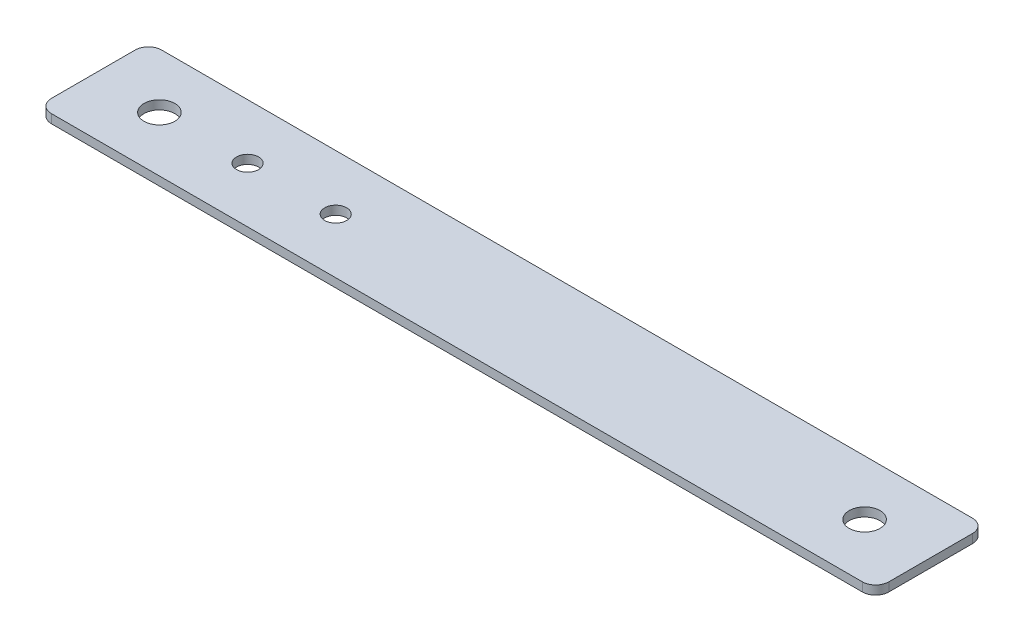
SolidWorks part; units mm, degrees
ref_plane "Front Plane" through (0, 0, 0) normal (0, 0, 1) x (1, 0, 0)
ref_plane "Top Plane" through (0, 0, 0) normal (0, 1, 0) x (1, 0, 0)
ref_plane "Right Plane" through (0, 0, 0) normal (1, 0, 0) x (0, 0, -1)
sketch "Sketch1" plane through (0, 0, 0) normal (0, 1, 0) x (1, 0, 0)
  line L1 (92, -12.5) -> (-92, -12.5)
  line L2 (95, -9.5) -> (95, 9.5)
  line L3 (92, 12.5) -> (-92, 12.5)
  line L4 (-95, -9.5) -> (-95, 9.5)
  line L5 (95, -12.5) -> (-95, 12.5) construction
  line L6 (95, 12.5) -> (-95, -12.5) construction
  arc A0 (-92, -12.5) -> (-95, -9.5) centre (-92, -9.5) cw
  arc A1 (95, 9.5) -> (92, 12.5) centre (92, 9.5) ccw
  arc A2 (92, -12.5) -> (95, -9.5) centre (92, -9.5) ccw
  arc A3 (-92, 12.5) -> (-95, 9.5) centre (-92, 9.5) ccw
  point P0 (0, 0)
  dimension "D3" = 3
  dimension "D1" = 190
  dimension "D2" = 25
base flange "Base-Flange1" sketch "Sketch1" thickness 2 reverse thickness direction yes parameters "D1"=9
sketch "Sketch8" plane through (0, 2, 0) normal (0, 1, 0) x (1, 0, 0)
  line L0 (-95, 9.5) -> (-95, -9.5) construction
  line L1 (-92, -12.5) -> (92, -12.5) construction
  line L2 (95, -9.5) -> (95, 9.5) construction
  point P0 (-80, 0)
  point P2 (80, 0)
  dimension "D1" = 15
  dimension "D2" = 12.5
  dimension "D3" = 15
hole_wizard "Ø5.0mm Dowel Hole1" positions "Sketch8" profile "Sketch7" hole size "Ø5.0" standard "ISO" end condition through all
sketch "Sketch7" plane through (-80, 2, 0) normal (1, 0, 0) x (0, 0, 1)
  line L0 (0, 0) -> (0, 2)
  line L1 (0, 2) -> (3.5, 2)
  line L2 (3.5, 2) -> (3.5, 0)
  line L5 (3.5, 0) -> (0, 0)
  line L11 (0, -6.35) -> (0, 107.95) construction
  dimension "Thru Hole Dia." = 7
  dimension "Thru Hole Depth" = 2
sketch "Sketch11" plane through (0, 2, 0) normal (0, 1, 0) x (1, 0, 0)
  circle A0 centre (-80, 0) radius 3.5 construction
  point P0 (-60, 0)
  point P2 (-40, 0)
  dimension "D1" = 20
  dimension "D2" = 20
hole_wizard "Ø5.0mm Dowel Hole2" positions "Sketch11" profile "Sketch10" hole size "Ø5.0" standard "ISO" end condition through all
sketch "Sketch10" plane through (-60, 2, 0) normal (1, 0, 0) x (0, 0, 1)
  line L0 (0, 0) -> (0, 2)
  line L1 (0, 2) -> (2.5, 2)
  line L2 (2.5, 2) -> (2.5, 0)
  line L5 (2.5, 0) -> (0, 0)
  line L11 (0, -6.35) -> (0, 107.95) construction
  dimension "Thru Hole Dia." = 5
  dimension "Thru Hole Depth" = 2
sketch "Bend-Lines1" [suppressed] plane through (0, 0, 0) normal (0, 1, 0) x (1, 0, 0)
sketch "Bounding-Box1" [suppressed] plane through (0, 0, 0) normal (0, 1, 0) x (1, 0, 0)
sheet metal parameters "Sheet-Metal1" thickness 2 parameters "D1"=9
flat pattern "Flat-Pattern1" [suppressed]
sketch "Bend-Lines2" plane through (0, 0, 0) normal (0, 1, 0) x (1, 0, 0)
sketch3d "Bounding-Box2" [suppressed]
  line L0 (187, 22, 0) -> (-3, 22, 0) construction
  line L1 (187, -3, 0) -> (-3, -3, 0) construction
  line L2 (187, 22, 0) -> (187, -3, 0) construction
  line L3 (-3, 22, 0) -> (-3, -3, 0) construction
sheet metal parameters "Sheet-Metal2" thickness 2 parameters "D1"=9
flat pattern "Flat-Pattern1"
sketch "Bend-Lines2" plane through (0, 0, 0) normal (0, 1, 0) x (1, 0, 0)
sketch3d "Bounding-Box2" [suppressed]
  line L0 (-187, 22, 0) -> (3, 22, 0) construction
  line L1 (-187, -3, 0) -> (3, -3, 0) construction
  line L2 (-187, 22, 0) -> (-187, -3, 0) construction
  line L3 (3, 22, 0) -> (3, -3, 0) construction
sheet metal parameters "Sheet-Metal3" thickness 2 parameters "D1"=9
flat pattern "Flat-Pattern1"
sketch "Bend-Lines2" plane through (0, 0, 0) normal (0, 1, 0) x (1, 0, 0)
sketch3d "Bounding-Box2" [suppressed]
  line L0 (-187, 22, 0) -> (3, 22, 0) construction
  line L1 (-187, -3, 0) -> (3, -3, 0) construction
  line L2 (-187, 22, 0) -> (-187, -3, 0) construction
  line L3 (3, 22, 0) -> (3, -3, 0) construction
